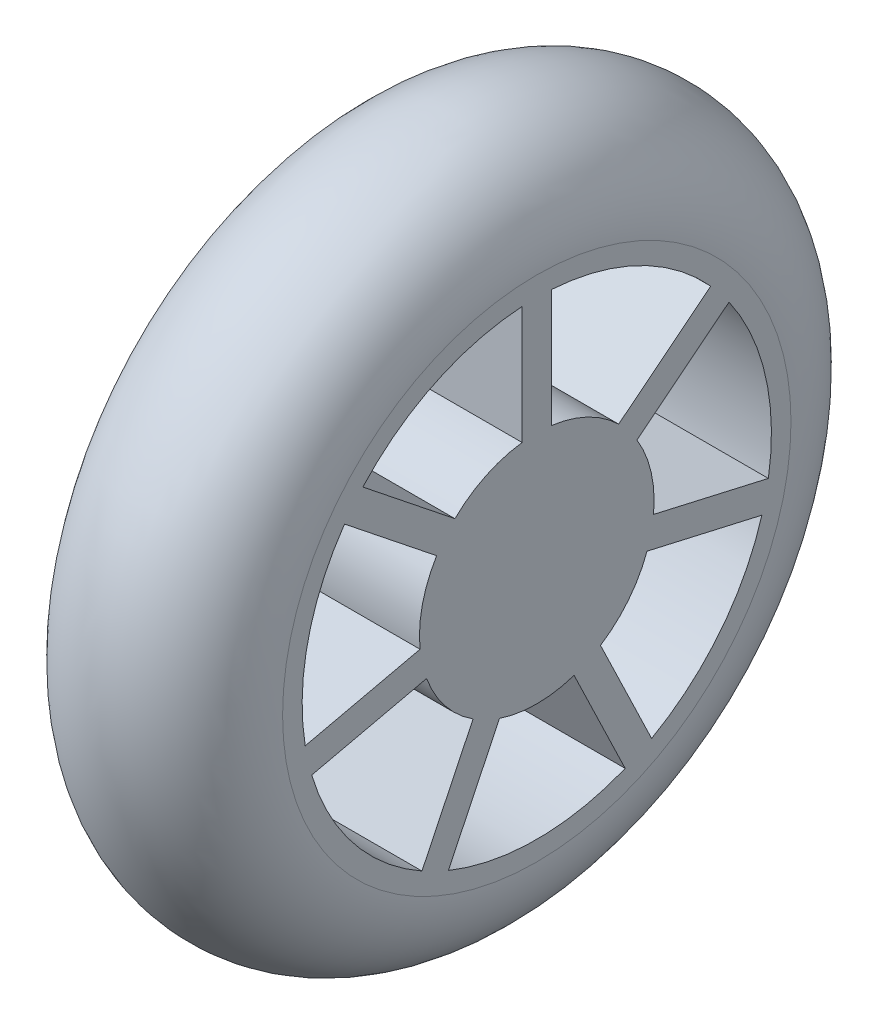
SolidWorks part; units mm, degrees
ref_plane "Front Plane" through (0, 0, 0) normal (0, 0, 1) x (1, 0, 0)
ref_plane "Top Plane" through (0, 0, 0) normal (0, 1, 0) x (1, 0, 0)
ref_plane "Right Plane" through (0, 0, 0) normal (1, 0, 0) x (0, 0, -1)
sketch "Sketch1" plane through (0, 0, 0) normal (0, 0, 1) x (1, 0, 0)
  line L1 (0, 0) -> (20, 0)
  line L2 (0, 0) -> (0, 26)
  line L4 (20, 0) -> (20, 26)
  arc A0 (20, 26) -> (0, 26) centre (10, 26) ccw
  dimension "D2" = 10
  dimension "D1" = 26
revolve "Revolve1" add sketch "Sketch1" angle 360 about L1
sketch "Sketch2" plane through (20, 0, 0) normal (1, 0, 0) x (0, 0, -1)
  line L0 (0, 0) -> (0, 24) construction
  line L1 (-1.5, 11.9059) -> (-1.5, 23.9531)
  line L2 (1.5, 11.9059) -> (1.5, 23.9531)
  line L3 (8.3732, 8.5959) -> (17.792, 16.1072)
  line L4 (10.2436, 6.2504) -> (19.6625, 13.7618)
  line L5 (11.9412, -1.1869) -> (23.6863, -3.8677)
  line L6 (11.2736, -4.1117) -> (23.0187, -6.7925)
  line L7 (6.5172, -10.076) -> (11.7443, -20.9302)
  line L8 (3.8143, -11.3777) -> (9.0414, -22.2318)
  line L9 (-3.8143, -11.3777) -> (-9.0414, -22.2318)
  line L10 (-6.5172, -10.076) -> (-11.7443, -20.9302)
  line L11 (-11.2736, -4.1117) -> (-23.0187, -6.7925)
  line L12 (-11.9412, -1.1869) -> (-23.6863, -3.8677)
  line L13 (-10.2436, 6.2504) -> (-19.6625, 13.7618)
  line L14 (-8.3732, 8.5959) -> (-17.792, 16.1072)
  circle A0 centre (0, 0) radius 12
  circle A1 centre (0, 0) radius 24
  point P36 (0, 0)
  dimension "D1" = 24
  dimension "D2" = 48
  dimension "D3" = 1.5
  dimension "D4" = 1.5
  dimension "D5" = 7
extrude "Cut-Extrude1" cut sketch "Sketch2" against normal through all contours L11 A1 L10 A0 | L9 A1 L8 A0 | L7 A1 L6 A0 | L5 A1 L4 A0 | L3 A1 L2 A0 | L1 A1 L14 A0 | L13 A1 L12 A0 region at (20, 16.5728, 7.9811) region at (20, 16.5728, -7.9811) region at (20, 4.0932, 17.9333) region at (20, 4.0932, -17.9333) region at (20, -11.4688, 14.3814) region at (20, -11.4688, -14.3814) region at (20, -18.3945, 0)
